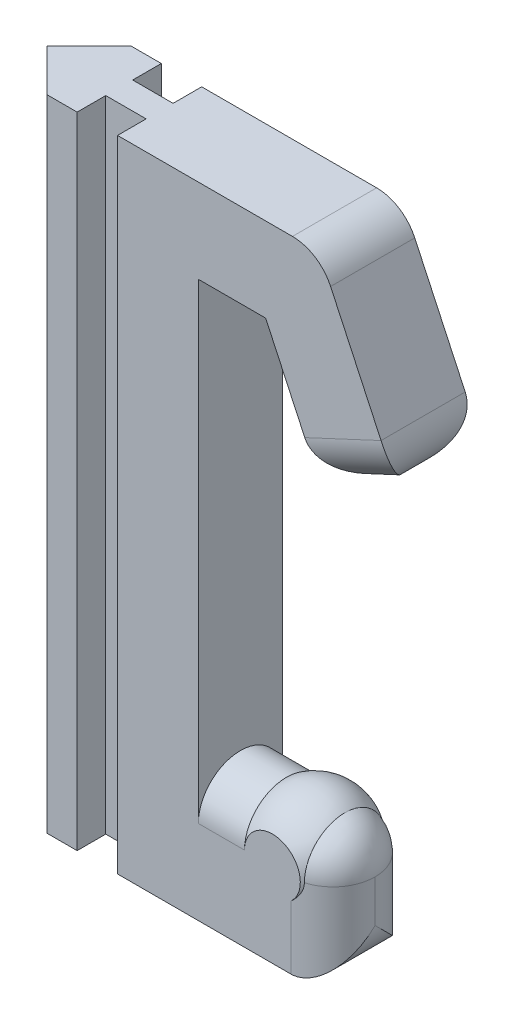
SolidWorks part; units mm, degrees
ref_plane "前视基准面" through (0, 0, 0) normal (0, 0, 1) x (1, 0, 0)
ref_plane "上视基准面" through (0, 0, 0) normal (0, 1, 0) x (1, 0, 0)
ref_plane "右视基准面" through (0, 0, 0) normal (1, 0, 0) x (0, 0, -1)
sketch "草图1" plane through (0, 0, 0) normal (0, 0, 1) x (1, 0, 0)
  line L0 (0, 0) -> (0, 28)
  line L1 (0, 28) -> (4, 28)
  line L2 (4, 28) -> (7.3809, 20.7495)
  line L3 (0, 0) -> (8, 0)
  line L4 (8, 0) -> (8, -5)
  line L5 (8, -5) -> (-5, -5)
  line L6 (7.3809, 20.7495) -> (11.9125, 22.8626)
  line L7 (11.9125, 22.8626) -> (7.1854, 33)
  line L8 (-5, 33) -> (7.1854, 33)
  line L9 (-5, 33) -> (-5, -5)
  point P10 (-4.733, -5)
  dimension "D1" = 4
  dimension "D2" = 65
  dimension "D3" = 28
  dimension "D4" = 8
  dimension "D5" = 5
  dimension "D6" = 5
  dimension "D7" = 5
  dimension "D9" = 5
  dimension "D10" = 8
extrude "凸台-拉伸1" add sketch "草图1" along normal blind 5
fillet "圆角1" radius 2.5 5 edges at (7.3809, 20.7495, 2.5) (9.6467, 21.8061, 5) (11.9125, 22.8626, 2.5) (9.6467, 21.8061, 0) (7.1854, 33, 2.5)
sketch "草图3" plane through (0, 0, 0) normal (1, 0, 0) x (0, 0, -1)
  line L0 (-5, 0) -> (0, 0) construction
  line L1 (-5, 0) -> (0, 0)
  arc A0 (0, 0) -> (-5, 0) centre (-2.5, 0) ccw
extrude "凸台-拉伸2" add sketch "草图3" along normal up to surface (8 mm away) up to face at (8, -2.5, 2.5)
fillet "圆角3" radius 2.5 4 edges at (8, -2.5, 5) (8, -2.5, 0) (8, -5, 2.5) (8, 2.5, 2.5)
ref_plane "基准面1" through (4.4, 0, 0) normal (1, 0, 0) x (0, 0, -1)
sketch "草图4" plane through (4.4, 0, 0) normal (1, 0, 0) x (0, 0, -1)
  line L0 (-2.5, 0) -> (0.5, 0) construction
  line L1 (-5.5, 0) -> (0.5, 0)
  arc A0 (0.5, 0) -> (-5.5, 0) centre (-2.5, 0) ccw
revolve "旋转3" add sketch "草图4" angle 360 about L0
sketch "草图5" plane through (-5, 0, 0) normal (-1, 0, 0) x (0, 0, 1)
  line L0 (0, -2.0992) -> (-1.4678, -2.0992)
  line L1 (0, 33) -> (0, -5) construction
  line L2 (-1.4678, -2.0992) -> (-1.4678, 2.0791)
  line L3 (-1.4678, 2.0791) -> (0, 2.0791)
  line L4 (0, 2.0791) -> (0, -2.0992)
  line L5 (5, -2.0992) -> (6.3896, -2.0992)
  line L6 (5, 33) -> (5, -5) construction
  line L7 (6.3896, -2.0992) -> (6.3896, 2.0791)
  line L8 (6.3896, 2.0791) -> (5, 2.0791)
  line L9 (5, 2.0791) -> (5, -2.0992)
extrude "切除-拉伸1" cut sketch "草图5" against normal blind 20
sketch "草图6" plane through (0, -5, 0) normal (0, -1, 0) x (1, 0, 0)
  line L0 (-5, 2.5) -> (-9.1141, 2.5) construction
  line L1 (-5, 5) -> (-5, 0) construction
  line L2 (-5, 2.5) -> (-5, 3.5)
  line L3 (-5, 3.5) -> (-7, 3.5)
  line L4 (-7, 3.5) -> (-7, 5)
  line L5 (-7, 5) -> (-9, 5)
  line L7 (-7, 0) -> (-9, 0)
  line L8 (-7, 1.5) -> (-7, 0)
  line L9 (-5, 1.5) -> (-7, 1.5)
  line L10 (-5, 2.5) -> (-5, 1.5)
  line L11 (-9, 5) -> (-11.5, 2.5)
  line L12 (-11.5, 2.5) -> (-9, 0)
  point P10 (-9, 2.5)
  point P13 (0, 0)
  dimension "D1" = 2
  dimension "D2" = 2
  dimension "D3" = 2
  dimension "D4" = 5
  dimension "D5" = 45
extrude "凸台-拉伸3" add sketch "草图6" against normal up to surface (38 mm away) up to face at (0.2963, 33, 2.5)
sketch "草图7" plane through (0, -5, 0) normal (0, -1, 0) x (1, 0, 0)
  line L3 (-7.2, 5) -> (-4.8, 5)
  line L4 (-11.5, 2.5) -> (-9.6964, 2.5) construction
  line L5 (-7.2, 1.7) -> (-7.2, 0)
  line L6 (-4.8, 5) -> (-4.8, 3.3)
  line L7 (-4.8, 3.3) -> (-7.2, 3.3)
  line L8 (-7.2, 3.3) -> (-7.2, 5)
  line L9 (-4.8, 5) -> (-4.8, 3.3)
  line L10 (-4.8, 3.3) -> (-7.2, 3.3)
  line L11 (-7.2, 3.3) -> (-7.2, 5)
  line L12 (-4.8, 1.7) -> (-7.2, 1.7)
  line L13 (-4.8, 0) -> (-4.8, 1.7)
  line L14 (-7.2, 0) -> (-4.8, 0)
  dimension "D1" = 0.2
extrude "切除-拉伸2" cut sketch "草图7" against normal up to surface (38 mm away) up to face at (-5.1011, 33, 2.5)
